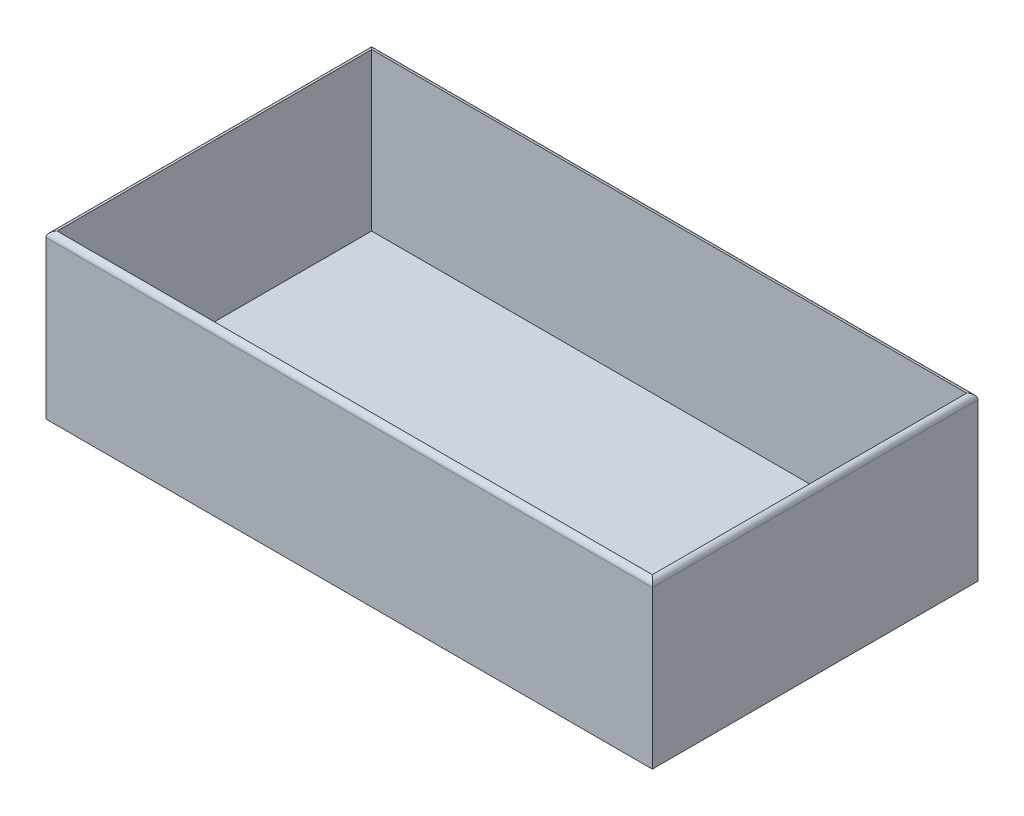
SolidWorks part; units mm, degrees
ref_plane "Front Plane" through (0, 0, 0) normal (0, 0, 1) x (1, 0, 0)
ref_plane "Top Plane" through (0, 0, 0) normal (0, 1, 0) x (1, 0, 0)
ref_plane "Right Plane" through (0, 0, 0) normal (1, 0, 0) x (0, 0, -1)
sketch "Sketch1" plane through (0, 0, 0) normal (0, 1, 0) x (1, 0, 0)
  line L1 (-54, 29) -> (54, 29)
  line L2 (-54, 29) -> (-54, -29)
  line L3 (-54, -29) -> (54, -29)
  line L4 (54, 29) -> (54, -29)
  line L5 (-54, 29) -> (54, -29) construction
  line L6 (-54, -29) -> (54, 29) construction
  point P0 (0, 0)
  dimension "D1" = 108
  dimension "D2" = 58
extrude "Boss-Extrude1" add sketch "Sketch1" along normal blind 29
sketch "Sketch2" plane through (0, 29, 0) normal (0, 1, 0) x (1, 0, 0)
  line L0 (-54, 29) -> (-54, -29) construction
  line L1 (-53, -28) -> (53, -28)
  line L2 (-53, -28) -> (-53, 28)
  line L3 (-53, 28) -> (53, 28)
  line L4 (53, -28) -> (53, 28)
  line L5 (-53, -28) -> (53, 28) construction
  line L6 (-53, 28) -> (53, -28) construction
  line L7 (54, 29) -> (-54, 29) construction
  point P0 (0, 0)
  dimension "D1" = 1
  dimension "D2" = 1
extrude "Cut-Extrude1" cut sketch "Sketch2" against normal blind 28
fillet "Fillet2" radius 1 4 edges at (0, 29, -29) (54, 29, 0) (0, 29, 29) (-54, 29, 0)
